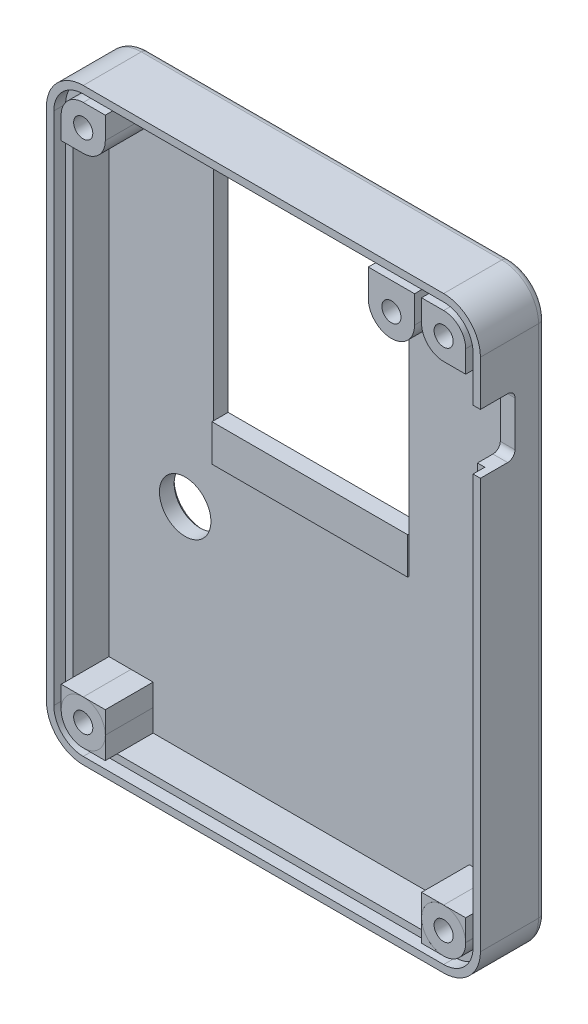
SolidWorks part; units mm, degrees
ref_plane "Спереди" through (0, 0, 0) normal (0, 0, 1) x (1, 0, 0)
ref_plane "Сверху" through (0, 0, 0) normal (0, 1, 0) x (1, 0, 0)
ref_plane "Справа" through (0, 0, 0) normal (1, 0, 0) x (0, 0, -1)
sketch "Эскиз1" plane through (0, 0, 0) normal (0, 0, 1) x (1, 0, 0)
  line L0 (29.5, 0) -> (29.5, -80) construction
  line L1 (0, 0) -> (59, 0)
  line L2 (0, 0) -> (0, -80)
  line L3 (0, -80) -> (59, -80)
  line L4 (59, 0) -> (59, -80)
  line L9 (29.5, -10) -> (29.5, -52.4) construction
  circle A1 centre (12.36, -49.17) radius 3.5
  dimension "D8" = 7
  dimension "D1" = 59
  dimension "D2" = 49.17
  dimension "D3" = 80
  dimension "D4" = 12.36
extrude "Бобышка-Вытянуть1" add sketch "Эскиз1" along normal blind 2.4
sketch "Эскиз4" plane through (0, 0, 2.4) normal (0, 0, 1) x (1, 0, 0)
  line L19 (0, 0) -> (59, 0)
  line L20 (0, 0) -> (0, -80)
  line L21 (0, -80) -> (59, -80)
  line L22 (59, 0) -> (59, -80)
  line L23 (5.1, -2) -> (53.9, -2)
  line L24 (2, -5.1) -> (2, -74.9)
  line L25 (5.1, -78) -> (53.9, -78)
  line L26 (57, -5.1) -> (57, -74.9)
  arc A0 (2, -74.9) -> (5.1, -78) centre (5.1, -74.9) ccw
  arc A1 (53.9, -78) -> (57, -74.9) centre (53.9, -74.9) ccw
  arc A2 (53.9, -2) -> (57, -5.1) centre (53.9, -5.1) cw
  arc A3 (5.1, -2) -> (2, -5.1) centre (5.1, -5.1) ccw
  dimension "D5" = 3.1
  dimension "D1" = 2
  dimension "D2" = 2
  dimension "D3" = 2
  dimension "D4" = 2
extrude "Бобышка-Вытянуть6" add sketch "Эскиз4" along normal blind 5.5
fillet "Скругление1" radius 5 1 edges at (0, 0, 3.95)
fillet "Скругление2" radius 5 3 edges at (0, -80, 3.95) (59, -80, 3.95) (59, 0, 3.95)
sketch "Эскиз14" plane through (0, 0, 2.4) normal (0, 0, 1) x (1, 0, 0)
  line L0 (0, -5) -> (0, -75) construction
  line L1 (59, -75) -> (59, -5) construction
  line L2 (5, -80) -> (54, -80) construction
  line L3 (5, -80) -> (54, -80) construction
  line L4 (54, 0) -> (5, 0) construction
  circle A0 centre (5, -5) radius 3
  circle A1 centre (5, -75) radius 3
  circle A2 centre (54, -75) radius 3
  circle A3 centre (54, -5) radius 3
  circle A4 centre (5, -5) radius 1.3
  circle A5 centre (54, -5) radius 1.3
  circle A6 centre (5, -75) radius 1.3
  circle A7 centre (54, -75) radius 1.3
  dimension "D1" = 5
  dimension "D2" = 5
  dimension "D3" = 5
  dimension "D4" = 5
  dimension "D5" = 5
  dimension "D6" = 5
  dimension "D7" = 5
  dimension "D8" = 5
  dimension "D9" = 2.6
  dimension "D10" = 6
  dimension "D11" = 2.6
extrude "Бобышка-Вытянуть7" add sketch "Эскиз14" along normal blind 6.5
sketch "Эскиз15" plane through (0, 0, 7.9) normal (0, 0, 1) x (1, 0, 0)
  line L0 (5, -80) -> (54, -80) construction
  line L5 (5, 0) -> (54, 0)
  line L6 (0, -5) -> (0, -75)
  line L7 (5, -80) -> (54, -80)
  line L8 (59, -5) -> (59, -75)
  line L9 (59, -75) -> (59, -5) construction
  line L10 (5, -1) -> (54, -1)
  line L11 (1, -5) -> (1, -75)
  line L12 (5, -79) -> (54, -79)
  line L13 (58, -5) -> (58, -75)
  arc A0 (0, -75) -> (5, -80) centre (5, -75) ccw
  arc A1 (54, -80) -> (59, -75) centre (54, -75) ccw
  arc A2 (54, 0) -> (59, -5) centre (54, -5) cw
  arc A3 (5, 0) -> (0, -5) centre (5, -5) ccw
  arc A4 (5, -1) -> (1, -5) centre (5, -5) ccw
  arc A5 (54, -1) -> (58, -5) centre (54, -5) cw
  arc A6 (54, -79) -> (58, -75) centre (54, -75) ccw
  arc A7 (1, -75) -> (5, -79) centre (5, -75) ccw
  point P23 (0, 0)
  dimension "D5" = 5
  dimension "D6" = 4
  dimension "D1" = 1
  dimension "D2" = 1
  dimension "D3" = 1
  dimension "D4" = 1
extrude "Бобышка-Вытянуть10" add sketch "Эскиз15" along normal blind 1 separate body
fillet "Скругление3" radius 1 8 edges at (57.5355, -1.4645, 0) (59, -40, 0) (57.5355, -78.5355, 0) (29.5, -80, 0) (1.4645, -78.5355, 0) (0, -40, 0) (1.4645, -1.4645, 0) (29.5, 0, 0)
sketch "Эскиз20" plane through (59, 0, 0) normal (1, 0, 0) x (0, 0, -1)
  line L0 (-8.9, -75) -> (-8.9, -5) construction
  line L1 (-8.9, -11.15) -> (-5.2, -11.15)
  line L2 (-8.9, -11.15) -> (-8.9, -19.25)
  line L3 (-8.9, -19.25) -> (-5.2, -19.25)
  line L4 (-4.2, -12.15) -> (-4.2, -18.25)
  line L5 (-7.9, 0) -> (-1, 0) construction
  arc A0 (-5.2, -19.25) -> (-4.2, -18.25) centre (-5.2, -18.25) ccw
  arc A1 (-5.2, -11.15) -> (-4.2, -12.15) centre (-5.2, -12.15) cw
  point P10 (-4.2, -19.25)
  point P13 (-4.2, -11.15)
  dimension "D4" = 1
  dimension "D1" = 8.1
  dimension "D2" = 4.7
  dimension "D3" = 11.15
extrude "Вырез-Вытянуть1" cut sketch "Эскиз20" against normal blind 10
sketch "Эскиз23" plane through (0, 0, 0) normal (0, 0, -1) x (-1, 0, 0)
  line L1 (-16.2, -7.241) -> (-42.8, -7.241)
  line L2 (-16.2, -7.241) -> (-16.2, -37.141)
  line L3 (-16.2, -37.141) -> (-42.8, -37.141)
  line L4 (-42.8, -7.241) -> (-42.8, -37.141)
  dimension "D1" = 29.9
  dimension "D2" = 26.6
extrude "Вырез-Вытянуть4" cut sketch "Эскиз23" against normal blind 52
ref_axis "Ось1" through (29.5, -1, 0) along (0, -1, 0)
sketch "Эскиз24" plane through (0, 0, 2.4) normal (0, 0, 1) x (1, 0, 0)
  line L0 (42.8, -7.241) -> (16.2, -7.241)
  line L1 (42.8, -7.241) -> (42.8, -2.241)
  line L2 (16.2, -7.241) -> (16.2, -2.241)
  line L3 (42.8, -2.241) -> (16.2, -2.241)
  dimension "D1" = 5
extrude "Бобышка-Вытянуть11" add sketch "Эскиз24" along normal blind 0.2
sketch "Эскиз25" plane through (0, 0, 2.4) normal (0, 0, 1) x (1, 0, 0)
  line L0 (16.2, -37.141) -> (42.8, -37.141)
  line L1 (16.2, -37.141) -> (16.2, -42.141)
  line L2 (42.8, -37.141) -> (42.8, -42.141)
  line L3 (16.2, -42.141) -> (42.8, -42.141)
  line L4 (16.2, -37.141) -> (42.8, -37.141) construction
  dimension "D1" = 5
extrude "Бобышка-Вытянуть12" add sketch "Эскиз25" along normal blind 0.2 contours L3 L2 L0 L1
sketch "Эскиз26" plane through (0, 0, 2.4) normal (0, 0, 1) x (1, 0, 0)
  circle A0 centre (46.9, -5.7) radius 1.3
  circle A1 centre (54, -5) radius 1.3 construction
  arc A3 (53.9504, -2.0004) -> (56.9996, -5.0496) centre (54, -5) ccw construction
  circle A4 centre (54, -5) radius 1.3 construction
  circle A5 centre (46.9, -5.7) radius 3.1474
  dimension "D1" = 2.6
  dimension "D3" = 0.7
  dimension "D4" = 7.1
  dimension "D2" = 3
extrude "Бобышка-Вытянуть13" add sketch "Эскиз26" along normal blind 6.5
sketch "Эскиз27" plane through (0, 0, 7.9) normal (0, 0, 1) x (1, 0, 0)
  line L12 (58, -75) -> (58, -19.25)
  line L13 (58, -19.25) -> (57, -19.25)
  line L14 (57, -19.25) -> (57, -74.9)
  line L15 (53.9, -78) -> (5.1, -78)
  line L16 (2, -74.9) -> (2, -5.1)
  line L17 (5.1, -2) -> (53.9, -2)
  line L18 (57, -5.1) -> (57, -11.15)
  line L19 (57, -11.15) -> (58, -11.15)
  line L20 (58, -11.15) -> (58, -5)
  line L21 (54, -1) -> (5, -1)
  line L22 (1, -5) -> (1, -75)
  line L23 (5, -79) -> (54, -79)
  line L24 (58, -75) -> (58, -19.25)
  line L25 (58, -19.25) -> (57, -19.25)
  line L26 (57, -19.25) -> (57, -74.9)
  line L27 (53.9, -78) -> (5.1, -78)
  line L28 (2, -74.9) -> (2, -5.1)
  line L29 (5.1, -2) -> (53.9, -2)
  line L30 (57, -5.1) -> (57, -11.15)
  line L31 (57, -11.15) -> (58, -11.15)
  line L32 (58, -11.15) -> (58, -5)
  line L33 (54, -1) -> (5, -1)
  line L34 (1, -5) -> (1, -75)
  line L35 (5, -79) -> (54, -79)
  arc A16 (54, -79) -> (58, -75) centre (54, -75) ccw
  arc A17 (56.9996, -74.9504) -> (57, -74.9) centre (53.9, -74.9) ccw
  arc A18 (53.9504, -77.9996) -> (56.9996, -74.9504) centre (54, -75) ccw
  arc A19 (53.9, -78) -> (53.9504, -77.9996) centre (53.9, -74.9) ccw
  arc A20 (5.0496, -77.9996) -> (5.1, -78) centre (5.1, -74.9) ccw
  arc A21 (2.0004, -74.9504) -> (5.0496, -77.9996) centre (5, -75) ccw
  arc A22 (2, -74.9) -> (2.0004, -74.9504) centre (5.1, -74.9) ccw
  arc A23 (2.0004, -5.0496) -> (2, -5.1) centre (5.1, -5.1) ccw
  arc A24 (5.0496, -2.0004) -> (2.0004, -5.0496) centre (5, -5) ccw
  arc A25 (5.1, -2) -> (5.0496, -2.0004) centre (5.1, -5.1) ccw
  arc A26 (53.9504, -2.0004) -> (53.9, -2) centre (53.9, -5.1) ccw
  arc A27 (56.9996, -5.0496) -> (53.9504, -2.0004) centre (54, -5) ccw
  arc A28 (57, -5.1) -> (56.9996, -5.0496) centre (53.9, -5.1) ccw
  arc A29 (58, -5) -> (54, -1) centre (54, -5) ccw
  arc A30 (5, -1) -> (1, -5) centre (5, -5) ccw
  arc A31 (1, -75) -> (5, -79) centre (5, -75) ccw
  arc A32 (54, -79) -> (58, -75) centre (54, -75) ccw
  arc A33 (56.9996, -74.9504) -> (57, -74.9) centre (53.9, -74.9) ccw
  arc A34 (53.9504, -77.9996) -> (56.9996, -74.9504) centre (54, -75) ccw
  arc A35 (53.9, -78) -> (53.9504, -77.9996) centre (53.9, -74.9) ccw
  arc A36 (5.0496, -77.9996) -> (5.1, -78) centre (5.1, -74.9) ccw
  arc A37 (2.0004, -74.9504) -> (5.0496, -77.9996) centre (5, -75) ccw
  arc A38 (2, -74.9) -> (2.0004, -74.9504) centre (5.1, -74.9) ccw
  arc A39 (2.0004, -5.0496) -> (2, -5.1) centre (5.1, -5.1) ccw
  arc A40 (5.0496, -2.0004) -> (2.0004, -5.0496) centre (5, -5) ccw
  arc A41 (5.1, -2) -> (5.0496, -2.0004) centre (5.1, -5.1) ccw
  arc A42 (53.9504, -2.0004) -> (53.9, -2) centre (53.9, -5.1) ccw
  arc A43 (56.9996, -5.0496) -> (53.9504, -2.0004) centre (54, -5) ccw
  arc A44 (57, -5.1) -> (56.9996, -5.0496) centre (53.9, -5.1) ccw
  arc A45 (58, -5) -> (54, -1) centre (54, -5) ccw
  arc A46 (5, -1) -> (1, -5) centre (5, -5) ccw
  arc A47 (1, -75) -> (5, -79) centre (5, -75) ccw
  dimension "D1" = 0
extrude "Вырез-Вытянуть5" cut sketch "Эскиз27" against normal blind 0.6
sketch "Эскиз28" plane through (0, 0, 2.4) normal (0, 0, 1) x (1, 0, 0)
  line L0 (5, -2) -> (8, -2)
  line L1 (53.9, -2) -> (5.1, -2) construction
  line L2 (8, -2) -> (8, -5)
  line L4 (5, -8) -> (2, -8)
  line L5 (2, -5.1) -> (2, -74.9) construction
  line L6 (2, -8) -> (2, -5.1)
  line L7 (2, -5.1) -> (2.0017, -5.1017)
  line L8 (51, -5) -> (51, -2)
  line L9 (57, -74.9) -> (57, -5.1) construction
  line L10 (57, -8) -> (54, -8)
  line L12 (57, -5) -> (57, -8)
  line L13 (5.1, -2) -> (53.9, -2) construction
  line L14 (51, -2) -> (54, -2)
  line L16 (43.7526, -5.7) -> (43.7526, -2)
  line L17 (43.7526, -2) -> (50.0474, -2)
  line L18 (50.0474, -2) -> (50.0474, -5.7)
  circle A0 centre (5, -5) radius 3 construction
  arc A1 (2.0004, -5.0496) -> (5.0496, -2.0004) centre (5, -5) ccw construction
  arc A2 (53.9504, -2.0004) -> (56.9996, -5.0496) centre (54, -5) ccw construction
  arc A3 (56.9996, -5.0496) -> (53.9504, -2.0004) centre (54, -5) ccw construction
  circle A4 centre (54, -5) radius 3 construction
  circle A5 centre (46.9, -5.7) radius 3.1474 construction
  circle A6 centre (46.9, -5.7) radius 3.1474 construction
  arc A12 (2.0017, -5.1017) -> (5, -8) centre (5, -5) ccw
  arc A13 (8, -5) -> (5, -2) centre (5, -5) ccw
  arc A14 (50.0474, -5.7) -> (43.7526, -5.7) centre (46.9, -5.7) ccw
  arc A15 (54, -2) -> (51, -5) centre (54, -5) ccw
  arc A16 (54, -8) -> (57, -5) centre (54, -5) ccw
chamfer "Фаска1" distance 0.4 angle 45 4 edges at (42.8, -22.191, 0) (29.5, -7.241, 0) (16.2, -22.191, 0) (29.5, -37.141, 0)
chamfer "Фаска2" distance 0.4 angle 45 1 edges at (15.86, -49.17, 0)
sketch "Эскиз30" plane through (0, 0, 2.4) normal (0, 0, 1) x (1, 0, 0)
  line L0 (54, -72) -> (57, -72)
  line L1 (57, -74.9) -> (57, -5.1) construction
  line L2 (57, -72) -> (57, -75)
  line L3 (54, -72) -> (51, -72)
  line L4 (51, -72) -> (51, -75)
  line L5 (51, -75) -> (51, -78)
  line L6 (5.1, -78) -> (53.9, -78) construction
  line L7 (51, -78) -> (54, -78)
  line L8 (8, -75) -> (8, -72)
  line L9 (8, -72) -> (5, -72)
  line L10 (5, -72) -> (2, -72)
  line L11 (2, -74.9) -> (2, -5.1) construction
  line L12 (2, -72) -> (2.0004, -74.9504)
  line L13 (8, -75) -> (8, -78)
  line L14 (8, -78) -> (5.0496, -77.9996)
  arc A0 (57, -75) -> (54, -78) centre (54, -75) ccw
  arc A1 (5.0496, -77.9996) -> (2.0004, -74.9504) centre (5, -75) ccw construction
  circle A2 centre (5, -75) radius 3 construction
  arc A3 (5.0496, -77.9996) -> (2.0004, -74.9504) centre (5, -75) ccw
  arc M12 (2.0004, -74.9504) -> (5.0496, -77.9996) centre (5, -75) cw
  line M14 (5.1, -78) -> (53.9, -78)
  arc M15 (53.9, -78) -> (53.9504, -77.9996) centre (53.9, -74.9) ccw
  arc M16 (53.9504, -77.9996) -> (56.9996, -74.9504) centre (54, -75) cw
  arc M17 (56.9996, -74.9504) -> (57, -74.9) centre (53.9, -74.9) ccw
  line M18 (57, -74.9) -> (57, -5.1)
extrude "Бобышка-Вытянуть16" add sketch "Эскиз30" along normal up to surface (6.5 mm away) separate body contours L14 L13 M12 | L8 L9 M12 | L10 L12 M12 | L0 M16 M17 M18 | L3 L4 M16 | L5 M16 M14 M15 region at (51.6701, -72.6701, 2.4) region at (56.3299, -72.6701, 2.4) region at (2.6703, -72.6697, 2.4) region at (7.3299, -72.6701, 2.4) region at (7.3303, -77.3297, 2.4) region at (51.6701, -77.3299, 2.4) up to face at (57, -75, 8.9)
sketch "Эскиз31" plane through (0, 0, 2.4) normal (0, 0, 1) x (1, 0, 0)
  line L0 (5, -2) -> (8, -2)
  line L1 (8, -2) -> (8, -5)
  line L2 (8, -5) -> (5, -2)
  line L3 (5, -8) -> (2, -8)
  line L4 (2, -8) -> (2, -5.1)
  line L5 (2, -5.1) -> (5, -8)
  line L6 (50.0474, -5.7) -> (50.0474, -2)
  line L7 (50.0474, -2) -> (43.7526, -2)
  line L8 (43.7526, -2) -> (43.7539, -5.7904)
  line L9 (43.7539, -5.7904) -> (46.9, -2.5526)
  line L10 (46.9, -2.5526) -> (50.0474, -5.7)
  line L11 (57, -5) -> (54, -8)
  line L12 (54, -8) -> (57, -8)
  line L13 (57, -8) -> (57, -5)
  line L14 (54, -2) -> (51, -2)
  line L15 (51, -2) -> (51, -5)
  line L16 (51, -5) -> (54, -2)
  circle A0 centre (46.9, -5.7) radius 3.1474 construction
  arc A1 (50.0474, -5.7) -> (43.7526, -5.7) centre (46.9, -5.7) ccw construction
extrude "Бобышка-Вытянуть17" add sketch "Эскиз31" along normal up to surface (6.5 mm away) up to face at (50.0474, -5.7, 8.9)
sketch "Эскиз32" plane through (0, 0, 2.4) normal (0, 0, 1) x (1, 0, 0)
  line L0 (-1.9989, -9.1808) -> (60.3488, -9.1808)
  line L1 (60.3488, -9.1808) -> (59.1078, -83.5252)
  line L2 (59.1078, -83.5252) -> (-8.3232, -82.3995)
  line L3 (-8.3232, -82.3995) -> (-1.9989, -9.1808)
